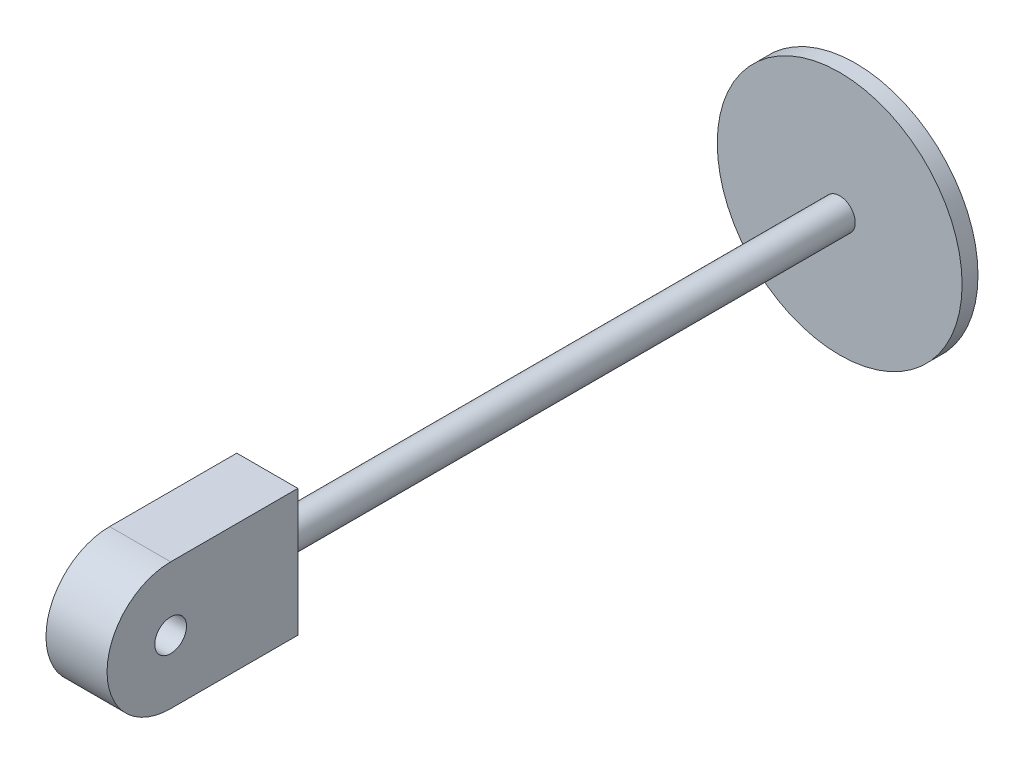
SolidWorks part; units mm, degrees
ref_plane "Front Plane" through (0, 0, 0) normal (0, 0, 1) x (1, 0, 0)
ref_plane "Top Plane" through (0, 0, 0) normal (0, 1, 0) x (1, 0, 0)
ref_plane "Right Plane" through (0, 0, 0) normal (1, 0, 0) x (0, 0, -1)
sketch "Sketch1" plane through (0, 0, 0) normal (0, 0, 1) x (1, 0, 0)
  circle A0 centre (0, 0) radius 9.625
  dimension "D1" = 19.25
extrude "Boss-Extrude1" add sketch "Sketch1" along normal mid plane 1.25
sketch "Sketch2" plane through (0, 0, 0.625) normal (0, 0, 1) x (1, 0, 0)
  circle A0 centre (0, 0) radius 1.225
  dimension "D1" = 2.45
extrude "Boss-Extrude2" add sketch "Sketch2" along normal blind 45
sketch "Sketch3" plane through (0, 0, 0) normal (1, 0, 0) x (0, 0, -1)
  line L0 (-45.625, 5) -> (-45.625, -5)
  line L1 (-45.625, 1.225) -> (-45.625, -1.225) construction
  line L2 (-45.625, 5) -> (-55.625, 5)
  line L4 (-55.625, -5) -> (-45.625, -5)
  arc A0 (-55.625, 5) -> (-55.625, -5) centre (-55.625, 0) ccw
  point P4 (-45.625, 0)
  dimension "D3" = 5
  dimension "D1" = 10
  dimension "D2" = 10
extrude "Boss-Extrude3" add sketch "Sketch3" along normal mid plane 4.8
sketch "Sketch4" plane through (-2.4, 0, 0) normal (-1, 0, 0) x (0, 0, 1)
  circle A0 centre (55.625, 0) radius 1.25
  arc A1 (55.625, -5) -> (55.625, 5) centre (55.625, 0) ccw construction
  dimension "D1" = 2.5
extrude "Cut-Extrude1" cut sketch "Sketch4" against normal blind 10
ref_axis "Axis2" through (2.4, 0, 55.625) along (-1, 0, 0)
ref_point "Point2"
ref_axis "Axis1" [suppressed] through (2.4, 0, 95.625) along (-1, 0, 0)
ref_point "Point1" [suppressed]
